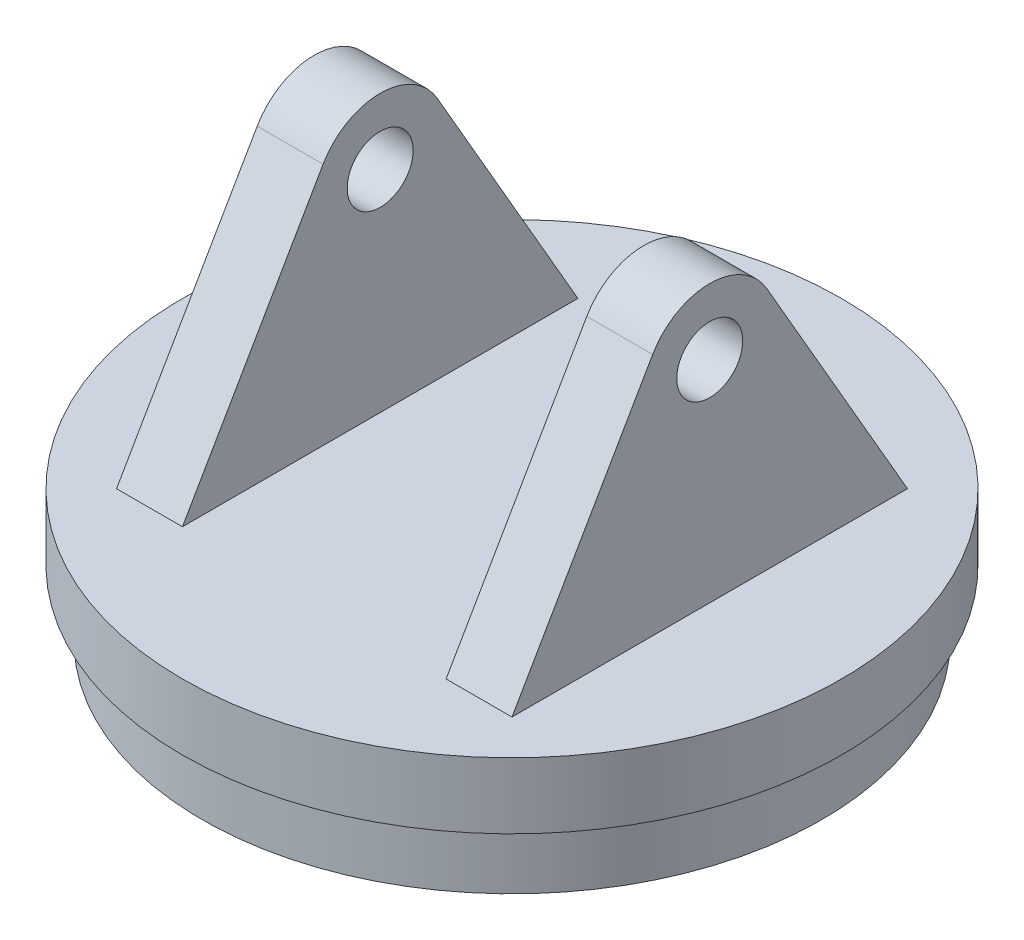
SolidWorks part; units mm, degrees
ref_plane "Front Plane" through (0, 0, 0) normal (0, 0, 1) x (1, 0, 0)
ref_plane "Top Plane" through (0, 0, 0) normal (0, 1, 0) x (1, 0, 0)
ref_plane "Right Plane" through (0, 0, 0) normal (1, 0, 0) x (0, 0, -1)
sketch "Sketch1" plane through (0, 0, 0) normal (0, 1, 0) x (1, 0, 0)
  circle A0 centre (0, 0) radius 50
  dimension "D1" = 100
extrude "Boss-Extrude1" add sketch "Sketch1" along normal blind 10
sketch "Sketch2" plane through (0, 0, 0) normal (1, 0, 0) x (0, 0, -1)
  line L0 (30, 10) -> (8.6603, 46.9615)
  line L1 (50, 10) -> (-50, 10) construction
  line L2 (-8.6603, 46.9615) -> (-30, 10)
  line L3 (30, 10) -> (-30, 10)
  line L4 (0, 10) -> (0, 58.7286) construction
  line L5 (0, 5.5) -> (0, -5.5) construction
  arc A0 (-8.6603, 46.9615) -> (8.6603, 46.9615) centre (0, 41.9615) cw
  circle A1 centre (0, 41.9615) radius 5
  point P14 (0, 61.9615)
  dimension "D4" = 10
  dimension "D5" = 10
  dimension "D1" = 60
  dimension "D2" = 60
  dimension "D3" = 60
extrude "Boss-Extrude2" add sketch "Sketch2" along normal blind 10 from offset 20
extrude "Boss-Extrude3" add sketch "Sketch2<2>" against normal blind 10 from offset 20 offset against normal yes
sketch "Sketch2<2>" plane through (0, 0, 0) normal (1, 0, 0) x (0, 0, -1) same geometry as "Sketch2"
sketch "Sketch3" plane through (0, 0, 0) normal (0, -1, 0) x (1, 0, 0)
  circle A2 centre (0, 0) radius 47
  circle A3 centre (0, 0) radius 47
  dimension "D1" = 3
extrude "Boss-Extrude4" add sketch "Sketch3" along normal blind 10
sketch "Sketch4" plane through (0, -10, 0) normal (0, -1, 0) x (1, 0, 0)
  circle A0 centre (0, 0) radius 2.5
  dimension "D1" = 5
extrude "Cut-Extrude1" cut sketch "Sketch4" against normal blind 10
